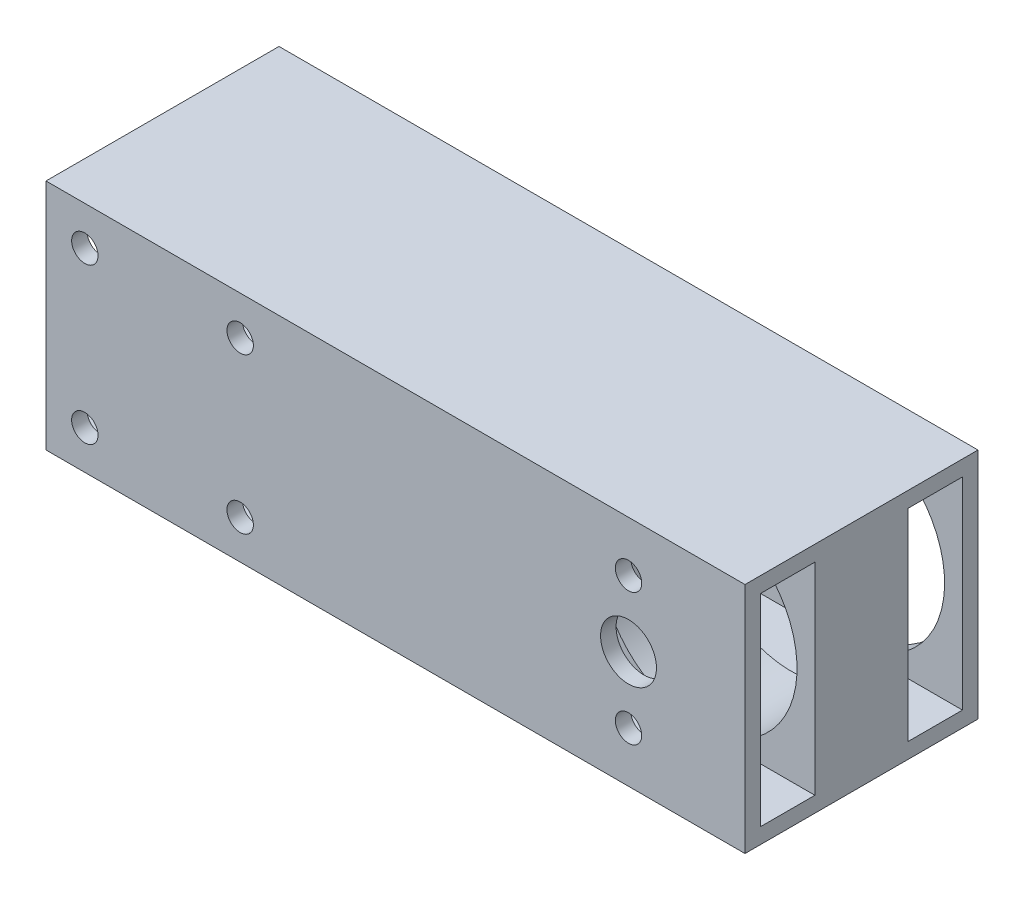
SolidWorks part; units mm, degrees
material "PLA 15%"
ref_plane "Front Plane" through (0, 0, 0) normal (0, 0, 1) x (1, 0, 0)
ref_plane "Top Plane" through (0, 0, 0) normal (0, 1, 0) x (1, 0, 0)
ref_plane "Right Plane" through (0, 0, 0) normal (1, 0, 0) x (0, 0, -1)
sketch "Sketch1" plane through (0, 0, 0) normal (1, 0, 0) x (0, 0, -1)
  line L1 (-15, -15) -> (15, -15)
  line L2 (-15, -15) -> (-15, 15)
  line L3 (-15, 15) -> (15, 15)
  line L4 (15, -15) -> (15, 15)
  line L5 (-15, -15) -> (15, 15) construction
  line L6 (-15, 15) -> (15, -15) construction
  line L11 (-5.1844, 5.1844) -> (5.1844, -5.1844) construction
  line L12 (-5.1844, -5.1844) -> (5.1844, 5.1844) construction
  line L13 (-13, 13) -> (-6, 13)
  line L14 (-13, 13) -> (-13, -13)
  line L15 (-13, -13) -> (-6, -13)
  line L16 (-6, 13) -> (-6, -13)
  line L17 (13, 13) -> (6, 13)
  line L18 (13, 13) -> (13, -13)
  line L19 (13, -13) -> (6, -13)
  line L20 (6, 13) -> (6, -13)
  point P0 (0, 0)
  point P7 (0, 0)
  dimension "D1" = 30
  dimension "D2" = 30
  dimension "D3" = 2
  dimension "D4" = 7
  dimension "D5" = 2
  dimension "D6" = 7
  dimension "D7" = 2
  dimension "D8" = 2
extrude "Boss-Extrude3" add sketch "Sketch1" along normal blind 90
sketch "Sketch6" plane through (0, 0, -15) normal (0, 0, -1) x (-1, 0, 0)
  line L0 (-90, -15) -> (-90, 15) construction
  circle A0 centre (-75, 0) radius 12.7
  dimension "D2" = 25.4
  dimension "D1" = 15
extrude "Cut-Extrude5" cut sketch "Sketch6" against normal blind 23
sketch "Sketch8" plane through (0, 0, 15) normal (0, 0, 1) x (1, 0, 0)
  line L0 (90, 15) -> (90, -15) construction
  line L1 (75, 0) -> (90, 0) construction
  circle A0 centre (75, 0) radius 3.6
  circle A1 centre (75, 8.5) radius 1.7
  circle A2 centre (75, -8.5) radius 1.7
  dimension "D2" = 7.2
  dimension "D5" = 3.4
  dimension "D1" = 15
  dimension "D3" = 17
extrude "Cut-Extrude6" cut sketch "Sketch8" against normal blind 17
sketch "Sketch9" plane through (0, 0, 0) normal (-1, 0, 0) x (0, 0, 1)
  line L0 (-6, 13) -> (6, 13)
  line L1 (-6, -13) -> (6, -13)
  line L2 (-6, 13) -> (-6, -13)
  line L3 (6, 13) -> (6, -13)
extrude "Cut-Extrude7" cut sketch "Sketch9" against normal blind 59
sketch "Sketch11" plane through (0, 0, 15) normal (0, 0, 1) x (1, 0, 0)
  line L13 (25, 10) -> (25, -10) construction
  line L16 (5, -10) -> (90, -10)
  line L17 (5, 10) -> (5, -10)
  line L18 (90, 10) -> (5, 10)
  line L19 (5, -10) -> (25, -10) construction
  line L20 (5, 10) -> (5, -10) construction
  line L21 (25, 10) -> (5, 10) construction
  point P12 (5, -10)
  point P14 (25, -10)
  point P15 (5, 10)
  point P16 (25, 10)
  dimension "D1" = 5
hole_wizard "M3 Clearance Hole1" positions "Sketch11" profile "Sketch12" hole size "M3" standard "ANSI Metric" end condition through all
sketch "Sketch12" plane through (25, 10, 15) normal (1, 0, 0) x (0, -1, 0)
  line L0 (0, 0) -> (0, 30)
  line L1 (0, 30) -> (1.7, 30)
  line L2 (1.7, 30) -> (1.7, 0)
  line L5 (1.7, 0) -> (0, 0)
  line L11 (0, -6.35) -> (0, 107.95) construction
  dimension "Thru Hole Dia." = 3.4
  dimension "Thru Hole Depth" = 30
